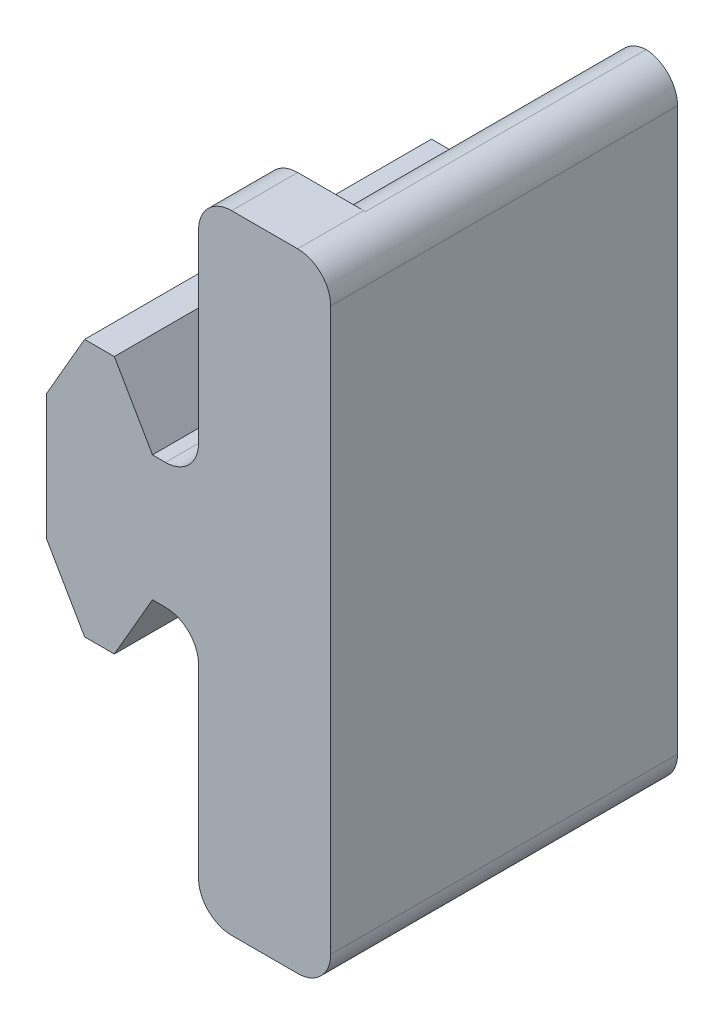
SolidWorks part; units mm, degrees
ref_plane "Alzado" through (0, 0, 0) normal (1, 0, 0) x (0, 1, 0)
ref_plane "Planta" through (0, 0, 0) normal (0, 0, 1) x (0, 1, 0)
ref_plane "Vista lateral" through (0, 0, 0) normal (0, 1, 0) x (-1, 0, 0)
sketch "Croquis1" plane through (0, 0, 0) normal (0, 0, 1) x (0, 1, 0)
  line L0 (-12.87, 0) -> (23.1864, 0) construction
  line L1 (0, 0) -> (0, 17.4542) construction
  line L2 (-3.8, 9.2094) -> (3.8, 9.2094)
  line L3 (3.8, 9.2094) -> (7.8, 6.9)
  line L4 (7.8, 6.9) -> (7.8, 5.1)
  line L5 (7.8, 5.1) -> (3.8, 2.7906)
  line L6 (3.8, 2.7906) -> (3.8, 0)
  line L7 (7.8, 6) -> (-7.8, 6) construction
  line L8 (3.8, 0) -> (19, 0)
  line L9 (19, 0) -> (19, -8)
  line L10 (19, -8) -> (-19, -8)
  line L11 (-19, 0) -> (-19, -8)
  line L12 (-3.8, 0) -> (-19, 0)
  line L13 (-3.8, 2.7906) -> (-3.8, 0)
  line L14 (-7.8, 5.1) -> (-3.8, 2.7906)
  line L15 (-7.8, 6.9) -> (-7.8, 5.1)
  line L16 (-3.8, 9.2094) -> (-7.8, 6.9)
  point P7 (0, 0)
  point P18 (0, 6)
  point P19 (0, -8)
  point P25 (0, 9.2094)
  dimension "D1" = 7.8
  dimension "D2" = 3.8
  dimension "D3" = 1.8
  dimension "D4" = 60
  dimension "D5" = 6
  dimension "D6" = 19
  dimension "D7" = 8
extrude "Saliente-Extruir1" add sketch "Croquis1" along normal blind 21
sketch "Croquis3" plane through (0, 0, 0) normal (0, 0, -1) x (1, 0, 0)
  line L0 (8, -19) -> (0, -19) construction
  line L1 (0, 19) -> (4.2, 19)
  line L2 (0, 19) -> (0, -19)
  line L3 (0, -19) -> (4.2, -19)
  line L4 (4.2, 19) -> (4.2, -19)
  dimension "D1" = 4.2
extrude "Cortar-Extruir1" cut sketch "Croquis3" against normal blind 17
fillet "Redondeo1" radius 2 8 edges at (8, 19, 10.5) (4.2, -19, 8.5) (8, -19, 10.5) (0, -3.8, 19) (0, 3.8, 19) (0, -19, 19) (0, 19, 19) (4.2, 19, 8.5)
